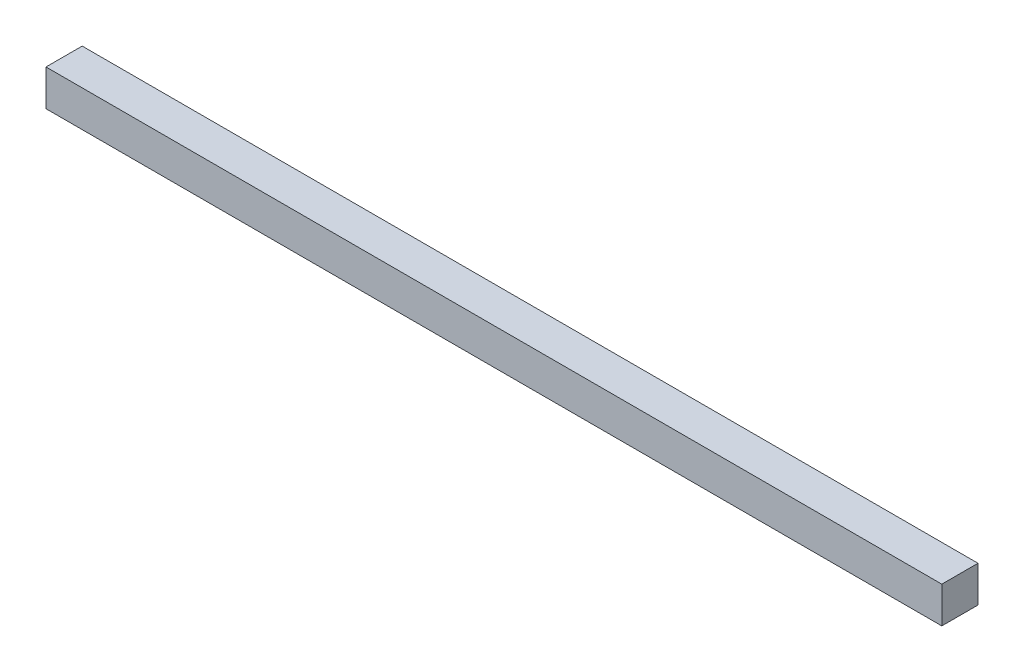
SolidWorks part; units mm, degrees
ref_plane "前视基准面" through (0, 0, 0) normal (0, 0, 1) x (1, 0, 0)
ref_plane "上视基准面" through (0, 0, 0) normal (0, 1, 0) x (1, 0, 0)
ref_plane "右视基准面" through (0, 0, 0) normal (1, 0, 0) x (0, 0, -1)
sketch "草图1" plane through (0, 0, 0) normal (0, 0, 1) x (1, 0, 0)
  line L1 (-74.4664, 33.35) -> (420.5336, 33.35)
  line L2 (-74.4664, 33.35) -> (-74.4664, 13.35)
  line L3 (-74.4664, 13.35) -> (420.5336, 13.35)
  line L4 (420.5336, 33.35) -> (420.5336, 13.35)
extrude "凸台-拉伸1" add sketch "草图1" along normal blind 10 and the other way blind 10
